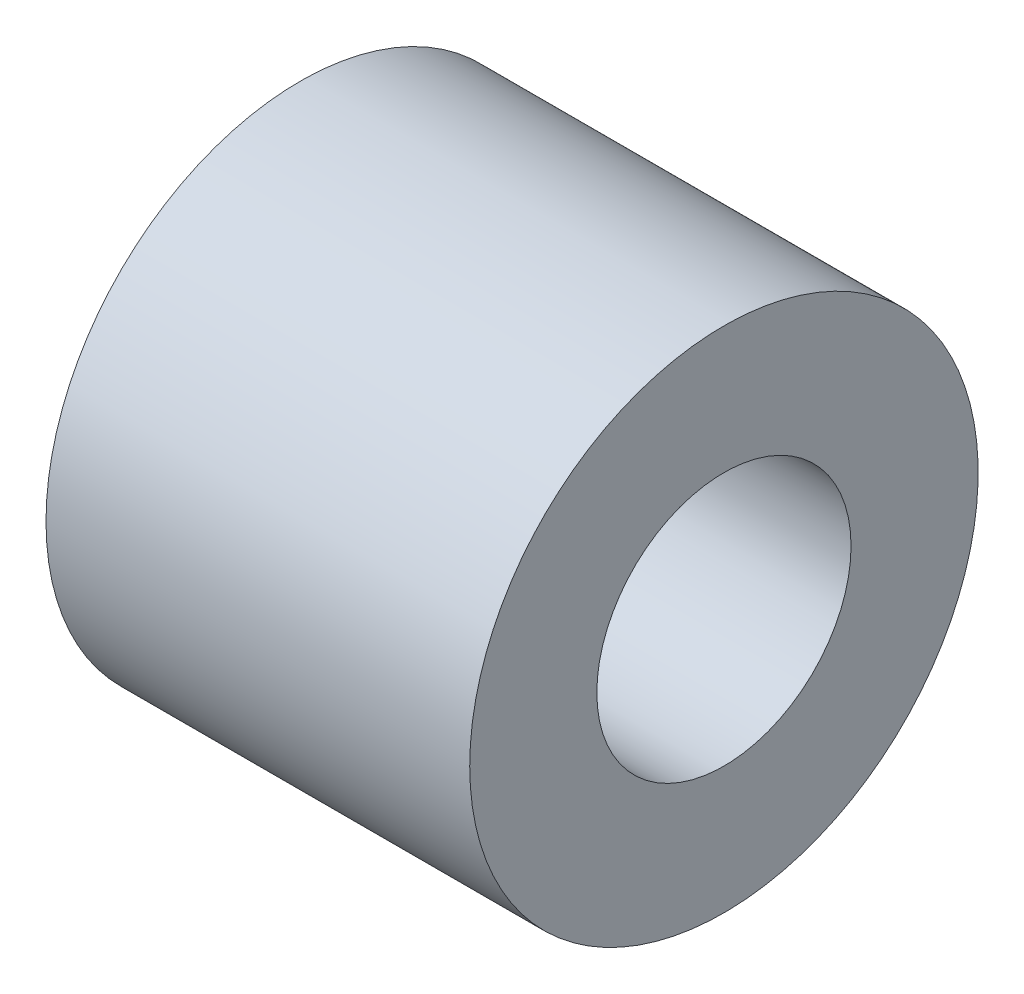
SolidWorks part; units mm, degrees
ref_plane "Front Plane" through (0, 0, 0) normal (0, 0, 1) x (1, 0, 0)
ref_plane "Top Plane" through (0, 0, 0) normal (0, 1, 0) x (1, 0, 0)
ref_plane "Right Plane" through (0, 0, 0) normal (1, 0, 0) x (0, 0, -1)
sketch "Stem_Coupler Sketch" plane through (0, 0, 0) normal (0, 0, 1) x (1, 0, 0)
  line L0 (-1000, 0) -> (1000, 0) construction
  line L1 (0, 3) -> (0, 6)
  line L2 (0, 6) -> (10, 6)
  line L3 (10, 6) -> (10, 3)
  line L4 (10, 3) -> (0, 3)
revolve "Stem_Coupler" add sketch "Stem_Coupler Sketch" angle 360 about L0
ref_axis "Engine Axis" through (10.5, 0, 0) along (-1, 0, 0)
